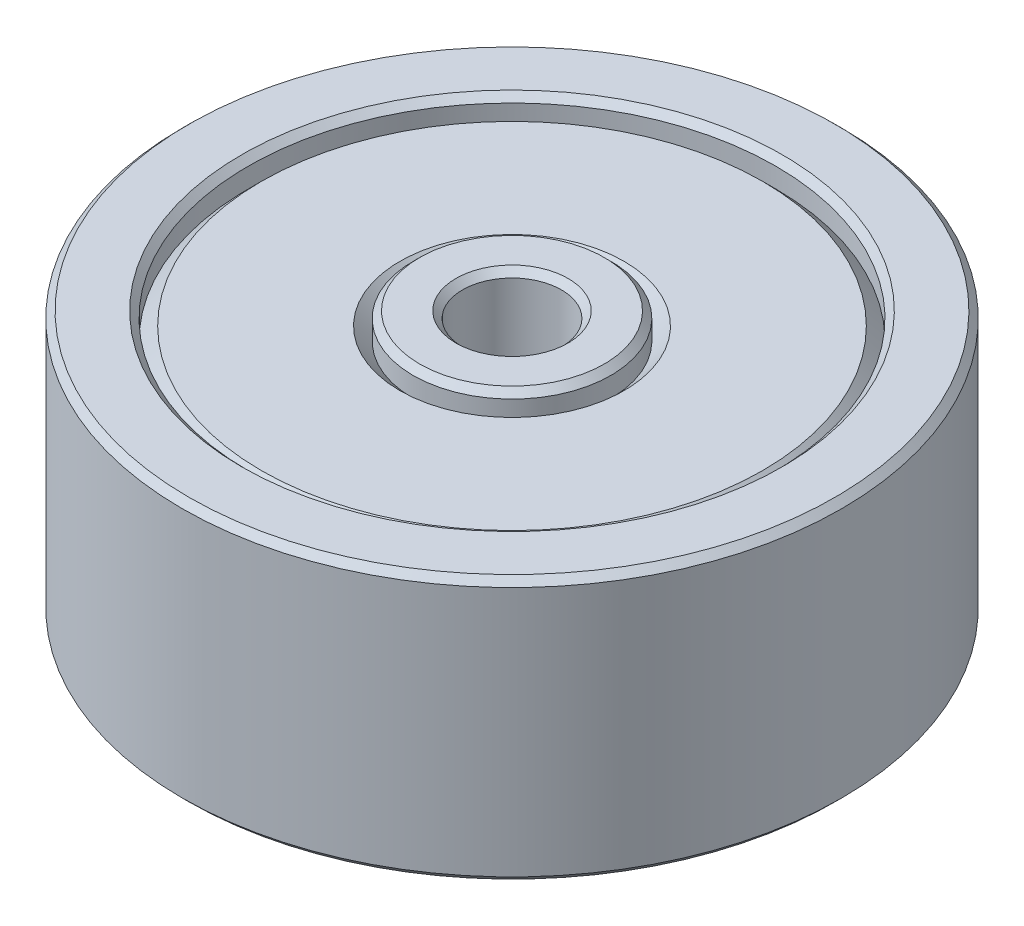
SolidWorks part; units mm, degrees
ref_plane "Front Plane" through (0, 0, 0) normal (0, 0, 1) x (1, 0, 0)
ref_plane "Top Plane" through (0, 0, 0) normal (0, 1, 0) x (1, 0, 0)
ref_plane "Right Plane" through (0, 0, 0) normal (1, 0, 0) x (0, 0, -1)
sketch "Sketch1" plane through (0, 0, 0) normal (1, 0, 0) x (0, 0, -1)
  line L1 (0, 2) -> (5, 2)
  line L2 (0, 2) -> (0, -2) construction
  line L3 (0, -2) -> (5, -2)
  line L4 (5, 2) -> (5, -2)
  line L6 (3.6, 0) -> (0, 0) construction
  line L7 (0.75, 2) -> (0.75, -2)
  point P9 (-0.6605, 1.786)
  point P13 (0, 0)
  dimension "D1" = 4
  dimension "D2" = 5
  dimension "D3" = 1.4
  dimension "D5" = 1.5
revolve "Revolve1" add sketch "Sketch1" angle 360 about L2 region at (0, 0, -2.875)
sketch "Sketch3" plane through (0, 0, 0) normal (1, 0, 0) x (0, 0, -1)
  line L0 (5, 2) -> (5, -2) construction
  line L1 (0.75, 2) -> (0.75, -2) construction
  line L2 (0, 2) -> (5, 2) construction
  line L3 (5, 2) -> (5, -2) construction
  line L4 (0.75, 2) -> (0.75, -2)
  line L5 (0, 2) -> (5, 2) construction
  line L6 (1.5, 2) -> (4, 2)
  line L7 (1.5, 2) -> (1.5, 1.6)
  line L8 (1.5, 1.6) -> (1.7, 1.8)
  line L9 (1.7, 1.8) -> (3.8, 1.8)
  line L10 (3.8, 1.8) -> (4, 1.6)
  line L11 (4, 1.6) -> (4, 2)
  line L14 (0, 2) -> (0, -2) construction
  line L17 (0, 2) -> (0, -2) construction
  line L18 (1.5, 1.6) -> (4, 1.6) construction
  line L19 (2.75, 1.6) -> (2.75, 2) construction
  point P11 (2.2272, 0)
  point P19 (0, 0)
  point P20 (3.0415, -0.2)
  dimension "D1" = 1
  dimension "D2" = 0.2
  dimension "D3" = 0.75
  dimension "D4" = 0.2
  dimension "D5" = 0.2
revolve "Cut-Revolve2" cut sketch "Sketch3" angle 360 about L17 region at (0, 1.8877, -2.75)
mirror "Mirror1" about plane through (0, 0, 0) normal (0, 1, 0) of "Cut-Revolve2"
chamfer "Chamfer1" distance 0.1 angle 45 8 edges at (0, -2, 4) (0, 2, 4) (0, -2, 5) (0, 2, 5) (0, -2, 1.5) (0, 2, 1.5) (0, -2, 0.75) (0, 2, 0.75)
